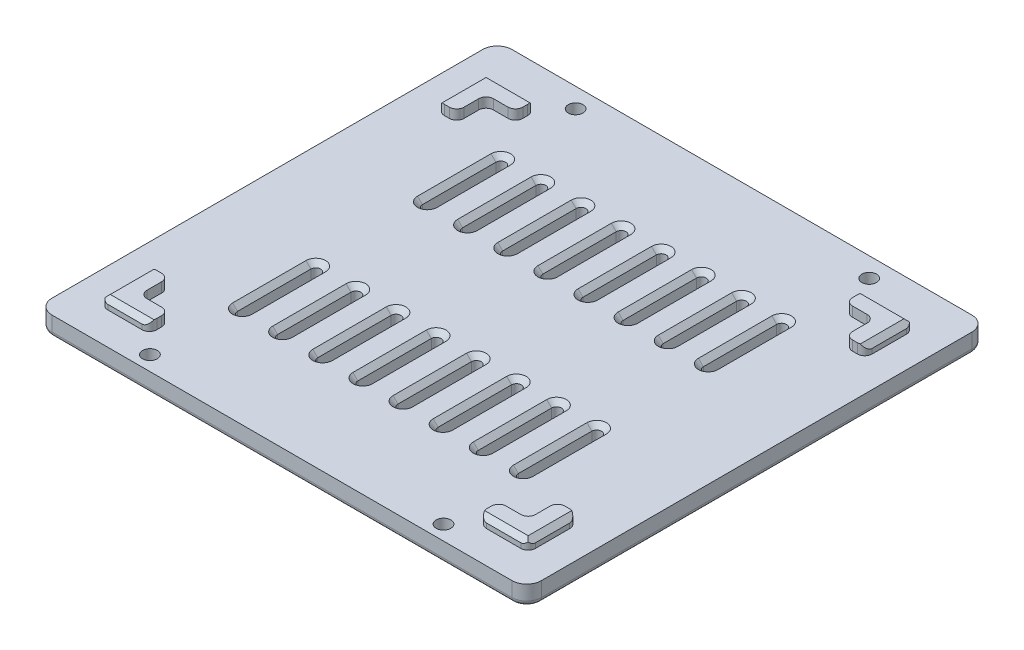
SolidWorks part; units mm, degrees
ref_plane "前基準面" through (0, 0, 0) normal (0, 0, 1) x (1, 0, 0)
ref_plane "上基準面" through (0, 0, 0) normal (0, 1, 0) x (1, 0, 0)
ref_plane "右基準面" through (0, 0, 0) normal (1, 0, 0) x (0, 0, -1)
sketch "草圖1" plane through (0, 0, 0) normal (0, 1, 0) x (1, 0, 0)
  line L1 (-50, -47) -> (50, -47)
  line L2 (-50, -47) -> (-50, 47)
  line L3 (-50, 47) -> (50, 47)
  line L4 (50, -47) -> (50, 47)
  line L5 (-50, -47) -> (50, 47) construction
  line L6 (-50, 47) -> (50, -47) construction
  point P0 (0, 0)
  dimension "D1" = 94
  dimension "D2" = 100
extrude "填料-伸長1" add sketch "草圖1" along normal blind 4
fillet "圓角1" radius 3 4 edges at (50, 2, 47) (-50, 2, 47) (50, 2, -47) (-50, 2, -47)
sketch "草圖2" plane through (0, 4, 0) normal (0, 1, 0) x (1, 0, 0)
  line L0 (-43.7, -30.4) -> (-43.7, -40.4)
  line L1 (-43.7, -40.4) -> (-33.7, -40.4)
  line L2 (-50, 44) -> (-50, -44) construction
  line L3 (-47, -47) -> (47, -47) construction
  line L4 (0, 0) -> (0, -25.4446) construction
  line L5 (43.7, -40.4) -> (33.7, -40.4)
  line L6 (43.7, -30.4) -> (43.7, -40.4)
  line L7 (-43.7, 28.4) -> (-43.7, 38.4)
  line L8 (-43.7, 38.4) -> (-33.7, 38.4)
  line L9 (47, 47) -> (-47, 47) construction
  line L10 (43.7, 38.4) -> (33.7, 38.4)
  line L11 (43.7, 28.4) -> (43.7, 38.4)
  line L12 (-39.7, -30.4) -> (-39.7, -36.4)
  line L13 (-39.7, -36.4) -> (-33.7, -36.4)
  line L14 (-43.7, -30.4) -> (-39.7, -30.4)
  line L15 (-33.7, -40.4) -> (-33.7, -36.4)
  line L16 (-39.7, 28.4) -> (-39.7, 34.4)
  line L17 (-39.7, 34.4) -> (-33.7, 34.4)
  line L18 (-43.7, 28.4) -> (-39.7, 28.4)
  line L19 (-33.7, 38.4) -> (-33.7, 34.4)
  line L20 (39.7, 28.4) -> (39.7, 34.4)
  line L21 (39.7, 34.4) -> (33.7, 34.4)
  line L22 (43.7, 28.4) -> (39.7, 28.4)
  line L23 (33.7, 38.4) -> (33.7, 34.4)
  line L24 (39.7, -30.4) -> (39.7, -36.4)
  line L25 (39.7, -36.4) -> (33.7, -36.4)
  line L26 (43.7, -30.4) -> (39.7, -30.4)
  line L27 (33.7, -40.4) -> (33.7, -36.4)
  dimension "D1" = 6.3
  dimension "D2" = 6.6
  dimension "D3" = 10
  dimension "D4" = 8.6
  dimension "D5" = 4
  dimension "D6" = 4
  dimension "D7" = 4
  dimension "D8" = 4
extrude "填料-伸長2" add sketch "草圖2" along normal blind 2
hole_wizard "CBORE for M2.5 Hex Socket Head Cap Screw1" positions "草圖3" profile "草圖4" counterbore size "M2.5" standard "ISO"
sketch "草圖3" plane through (0, 0, 0) normal (0, -1, 0) x (-1, 0, 0)
  circle A0 centre (-30, -44) radius 1.95 construction
  circle A1 centre (30, -44) radius 1.95 construction
  point P0 (-30, 43)
  point P2 (30, 43)
  point P4 (30, -44)
  point P6 (-30, -44)
  point P41 (0, 0)
  point P42 (-25.5791, 45.5332)
  point P43 (-30, 43)
  point P45 (0, 0)
  point P46 (0, 0)
  point P47 (0, 0)
  point P48 (0, 0)
  point P49 (30, 43)
  point P51 (0, 0)
sketch "草圖4" plane through (30, 0, -43) normal (1, 0, 0) x (0, 0, -1)
  line L0 (0, 0) -> (0, 10.9013)
  line L1 (0, 10.9013) -> (1.5, 10)
  line L2 (1.5, 10) -> (1.5, 1)
  line L3 (1.5, 1) -> (2.5, 1)
  line L4 (2.5, 1) -> (2.5, 0)
  line L5 (2.5, 0) -> (0, 0)
  line L10 (0, 10.9013) -> (-1.5, 10) construction
  line L11 (0, -6.35) -> (0, 107.95) construction
  dimension "Hole Dia." = 3
  dimension "Hole Depth" = 10
  dimension "C'Bore Dia." = 5
  dimension "C'Bore Depth" = 1
  dimension "Drill Angle" = 118
sketch "Sketch1" plane through (0, 4, 0) normal (0, 1, 0) x (1, 0, 0)
  line L0 (-28.7, -26.4) -> (-28.7, -11.4) construction
  line L1 (-29.7, -26.4) -> (-29.7, -11.4)
  line L2 (-27.7, -26.4) -> (-27.7, -11.4)
  line L3 (-39.7, -36.4) -> (-39.7, -30.4) construction
  line L4 (-20.5, -26.4) -> (-20.5, -11.4) construction
  line L5 (-21.5, -26.4) -> (-21.5, -11.4)
  line L6 (-19.5, -26.4) -> (-19.5, -11.4)
  line L7 (-12.3, -26.4) -> (-12.3, -11.4) construction
  line L8 (-13.3, -26.4) -> (-13.3, -11.4)
  line L9 (-11.3, -26.4) -> (-11.3, -11.4)
  line L10 (-4.1, -26.4) -> (-4.1, -11.4) construction
  line L11 (-5.1, -26.4) -> (-5.1, -11.4)
  line L12 (-3.1, -26.4) -> (-3.1, -11.4)
  line L13 (4.1, -26.4) -> (4.1, -11.4) construction
  line L14 (3.1, -26.4) -> (3.1, -11.4)
  line L15 (5.1, -26.4) -> (5.1, -11.4)
  line L16 (12.3, -26.4) -> (12.3, -11.4) construction
  line L17 (11.3, -26.4) -> (11.3, -11.4)
  line L18 (13.3, -26.4) -> (13.3, -11.4)
  line L19 (20.5, -26.4) -> (20.5, -11.4) construction
  line L20 (19.5, -26.4) -> (19.5, -11.4)
  line L21 (21.5, -26.4) -> (21.5, -11.4)
  line L22 (28.7, -26.4) -> (28.7, -11.4) construction
  line L23 (27.7, -26.4) -> (27.7, -11.4)
  line L24 (29.7, -26.4) -> (29.7, -11.4)
  line L25 (39.7, 34.4) -> (39.7, 28.4) construction
  line L26 (0, 0) -> (-35.579, 0) construction
  line L27 (-28.7, 26.4) -> (-28.7, 11.4) construction
  line L28 (-29.7, 26.4) -> (-29.7, 11.4)
  line L29 (-27.7, 26.4) -> (-27.7, 11.4)
  line L30 (-20.5, 26.4) -> (-20.5, 11.4) construction
  line L31 (-21.5, 26.4) -> (-21.5, 11.4)
  line L32 (-19.5, 26.4) -> (-19.5, 11.4)
  line L33 (-12.3, 26.4) -> (-12.3, 11.4) construction
  line L34 (-13.3, 26.4) -> (-13.3, 11.4)
  line L35 (-11.3, 26.4) -> (-11.3, 11.4)
  line L36 (-4.1, 26.4) -> (-4.1, 11.4) construction
  line L37 (-5.1, 26.4) -> (-5.1, 11.4)
  line L38 (-3.1, 26.4) -> (-3.1, 11.4)
  line L39 (4.1, 26.4) -> (4.1, 11.4) construction
  line L40 (3.1, 26.4) -> (3.1, 11.4)
  line L41 (5.1, 26.4) -> (5.1, 11.4)
  line L42 (12.3, 26.4) -> (12.3, 11.4) construction
  line L43 (11.3, 26.4) -> (11.3, 11.4)
  line L44 (13.3, 26.4) -> (13.3, 11.4)
  line L45 (20.5, 26.4) -> (20.5, 11.4) construction
  line L46 (19.5, 26.4) -> (19.5, 11.4)
  line L47 (21.5, 26.4) -> (21.5, 11.4)
  line L48 (28.7, 26.4) -> (28.7, 11.4) construction
  line L49 (27.7, 26.4) -> (27.7, 11.4)
  line L50 (29.7, 26.4) -> (29.7, 11.4)
  line L51 (-39.7, 34.4) -> (-33.7, 34.4) construction
  arc A0 (-29.7, -26.4) -> (-27.7, -26.4) centre (-28.7, -26.4) ccw
  arc A1 (-27.7, -11.4) -> (-29.7, -11.4) centre (-28.7, -11.4) ccw
  arc A2 (-21.5, -26.4) -> (-19.5, -26.4) centre (-20.5, -26.4) ccw
  arc A3 (-19.5, -11.4) -> (-21.5, -11.4) centre (-20.5, -11.4) ccw
  arc A4 (-13.3, -26.4) -> (-11.3, -26.4) centre (-12.3, -26.4) ccw
  arc A5 (-11.3, -11.4) -> (-13.3, -11.4) centre (-12.3, -11.4) ccw
  arc A6 (-5.1, -26.4) -> (-3.1, -26.4) centre (-4.1, -26.4) ccw
  arc A7 (-3.1, -11.4) -> (-5.1, -11.4) centre (-4.1, -11.4) ccw
  arc A8 (3.1, -26.4) -> (5.1, -26.4) centre (4.1, -26.4) ccw
  arc A9 (5.1, -11.4) -> (3.1, -11.4) centre (4.1, -11.4) ccw
  arc A10 (11.3, -26.4) -> (13.3, -26.4) centre (12.3, -26.4) ccw
  arc A11 (13.3, -11.4) -> (11.3, -11.4) centre (12.3, -11.4) ccw
  arc A12 (19.5, -26.4) -> (21.5, -26.4) centre (20.5, -26.4) ccw
  arc A13 (21.5, -11.4) -> (19.5, -11.4) centre (20.5, -11.4) ccw
  arc A14 (27.7, -26.4) -> (29.7, -26.4) centre (28.7, -26.4) ccw
  arc A15 (29.7, -11.4) -> (27.7, -11.4) centre (28.7, -11.4) ccw
  arc A16 (-29.7, 26.4) -> (-27.7, 26.4) centre (-28.7, 26.4) cw
  arc A17 (-27.7, 11.4) -> (-29.7, 11.4) centre (-28.7, 11.4) cw
  arc A18 (-21.5, 26.4) -> (-19.5, 26.4) centre (-20.5, 26.4) cw
  arc A19 (-19.5, 11.4) -> (-21.5, 11.4) centre (-20.5, 11.4) cw
  arc A20 (-13.3, 26.4) -> (-11.3, 26.4) centre (-12.3, 26.4) cw
  arc A21 (-11.3, 11.4) -> (-13.3, 11.4) centre (-12.3, 11.4) cw
  arc A22 (-5.1, 26.4) -> (-3.1, 26.4) centre (-4.1, 26.4) cw
  arc A23 (-3.1, 11.4) -> (-5.1, 11.4) centre (-4.1, 11.4) cw
  arc A24 (3.1, 26.4) -> (5.1, 26.4) centre (4.1, 26.4) cw
  arc A25 (5.1, 11.4) -> (3.1, 11.4) centre (4.1, 11.4) cw
  arc A26 (11.3, 26.4) -> (13.3, 26.4) centre (12.3, 26.4) cw
  arc A27 (13.3, 11.4) -> (11.3, 11.4) centre (12.3, 11.4) cw
  arc A28 (19.5, 26.4) -> (21.5, 26.4) centre (20.5, 26.4) cw
  arc A29 (21.5, 11.4) -> (19.5, 11.4) centre (20.5, 11.4) cw
  arc A30 (27.7, 26.4) -> (29.7, 26.4) centre (28.7, 26.4) cw
  arc A31 (29.7, 11.4) -> (27.7, 11.4) centre (28.7, 11.4) cw
  point P2 (-28.7, -18.9)
  point P13 (-20.5, -18.9)
  point P20 (-12.3, -18.9)
  point P27 (-4.1, -18.9)
  point P34 (4.1, -18.9)
  point P41 (12.3, -18.9)
  point P48 (20.5, -18.9)
  point P55 (28.7, -18.9)
  point P63 (-28.7, 18.9)
  point P73 (-20.5, 18.9)
  point P80 (-12.3, 18.9)
  point P87 (-4.1, 18.9)
  point P94 (4.1, 18.9)
  point P101 (12.3, 18.9)
  point P108 (20.5, 18.9)
  point P115 (28.7, 18.9)
  dimension "D1" = 2
  dimension "D2" = 10
  dimension "D3" = 15
  dimension "D5" = 10
  dimension "D6" = 8
  dimension "D4" = 8
extrude "Cut-Extrude1" cut sketch "Sketch1" against normal through all
chamfer "Chamfer1" distance 1 angle 45 8 edges at (43.7, 6, -33.4) (38.7, 6, -38.4) (-43.7, 6, -33.4) (-38.7, 6, -38.4) (-43.7, 6, 35.4) (-38.7, 6, 40.4) (38.7, 6, 40.4) (43.7, 6, 35.4)
fillet "圓角2" radius 1.5 24 edges at (43.7, 4.5, 30.4) (39.7, 5, 30.4) (39.7, 5, 36.4) (33.7, 5, 36.4) (33.7, 4.5, 40.4) (43.7, 4.5, 40.4) (43.7, 4.5, -38.4) (33.7, 4.5, -38.4) (33.7, 5, -34.4) (39.7, 5, -34.4) (39.7, 5, -28.4) (43.7, 4.5, -28.4) (-39.7, 5, -34.4) (-33.7, 5, -34.4) (-33.7, 4.5, -38.4) (-43.7, 4.5, -38.4) (-43.7, 4.5, -28.4) (-39.7, 5, -28.4) (-43.7, 4.5, 30.4) (-33.7, 4.5, 40.4) (-33.7, 5, 36.4) (-39.7, 5, 36.4) (-39.7, 5, 30.4) (-43.7, 4.5, 40.4)
chamfer "Chamfer2" distance 1 angle 45 128 edges at (-29.7, 0, -18.9) (-28.7, 0, -10.4) (-28.7, 0, -27.4) (-27.7, 0, -18.9) (-29.7, 4, -18.9) (-28.7, 4, -10.4) (-28.7, 4, -27.4) (-27.7, 4, -18.9) (-21.5, 0, -18.9) (-20.5, 0, -10.4) (-20.5, 0, -27.4) (-19.5, 0, -18.9) (-21.5, 4, -18.9) (-20.5, 4, -10.4) (-20.5, 4, -27.4) (-19.5, 4, -18.9) (-13.3, 0, -18.9) (-12.3, 0, -10.4) (-12.3, 0, -27.4) (-11.3, 0, -18.9) (-13.3, 4, -18.9) (-12.3, 4, -10.4) (-12.3, 4, -27.4) (-11.3, 4, -18.9) (-5.1, 0, -18.9) (-4.1, 0, -10.4) (-4.1, 0, -27.4) (-3.1, 0, -18.9) (-5.1, 4, -18.9) (-4.1, 4, -10.4) (-4.1, 4, -27.4) (-3.1, 4, -18.9) (3.1, 0, -18.9) (4.1, 0, -10.4) (4.1, 0, -27.4) (5.1, 0, -18.9) (3.1, 4, -18.9) (4.1, 4, -10.4) (4.1, 4, -27.4) (5.1, 4, -18.9) (11.3, 0, -18.9) (12.3, 0, -10.4) (12.3, 0, -27.4) (13.3, 0, -18.9) (11.3, 4, -18.9) (12.3, 4, -10.4) (12.3, 4, -27.4) (13.3, 4, -18.9) (19.5, 0, -18.9) (20.5, 0, -10.4) (20.5, 0, -27.4) (21.5, 0, -18.9) (19.5, 4, -18.9) (20.5, 4, -10.4) (20.5, 4, -27.4) (21.5, 4, -18.9) (27.7, 0, -18.9) (28.7, 0, -10.4) (28.7, 0, -27.4) (29.7, 0, -18.9) (27.7, 4, -18.9) (28.7, 4, -10.4) (28.7, 4, -27.4) (29.7, 4, -18.9) (27.7, 0, 18.9) (28.7, 0, 27.4) (28.7, 0, 10.4) (29.7, 0, 18.9) (27.7, 4, 18.9) (28.7, 4, 27.4) (28.7, 4, 10.4) (29.7, 4, 18.9) (19.5, 0, 18.9) (20.5, 0, 27.4) (20.5, 0, 10.4) (21.5, 0, 18.9) (19.5, 4, 18.9) (20.5, 4, 27.4) (20.5, 4, 10.4) (21.5, 4, 18.9) (11.3, 0, 18.9) (12.3, 0, 27.4) (12.3, 0, 10.4) (13.3, 0, 18.9) (11.3, 4, 18.9) (12.3, 4, 27.4) (12.3, 4, 10.4) (13.3, 4, 18.9) (3.1, 0, 18.9) (4.1, 0, 27.4) (4.1, 0, 10.4) (5.1, 0, 18.9) (3.1, 4, 18.9) (4.1, 4, 27.4) (4.1, 4, 10.4) (5.1, 4, 18.9) (-5.1, 0, 18.9) (-4.1, 0, 27.4) (-4.1, 0, 10.4) (-3.1, 0, 18.9) (-5.1, 4, 18.9) (-4.1, 4, 27.4) (-4.1, 4, 10.4) (-3.1, 4, 18.9) (-13.3, 0, 18.9) (-12.3, 0, 27.4) (-12.3, 0, 10.4) (-11.3, 0, 18.9) (-13.3, 4, 18.9) (-12.3, 4, 27.4) (-12.3, 4, 10.4) (-11.3, 4, 18.9) (-21.5, 0, 18.9) (-20.5, 0, 27.4) (-20.5, 0, 10.4) (-19.5, 0, 18.9) (-21.5, 4, 18.9) (-20.5, 4, 27.4) (-20.5, 4, 10.4) (-19.5, 4, 18.9) (-29.7, 0, 18.9) (-28.7, 0, 27.4) (-28.7, 0, 10.4) (-27.7, 0, 18.9) (-29.7, 4, 18.9) (-28.7, 4, 27.4) (-28.7, 4, 10.4) (-27.7, 4, 18.9)
fillet "Fillet1" radius 1 8 edges at (-49.1213, 0, -46.1213) (0, 0, -47) (49.1213, 0, -46.1213) (50, 0, 0) (49.1213, 0, 46.1213) (0, 0, 47) (-49.1213, 0, 46.1213) (-50, 0, 0)
